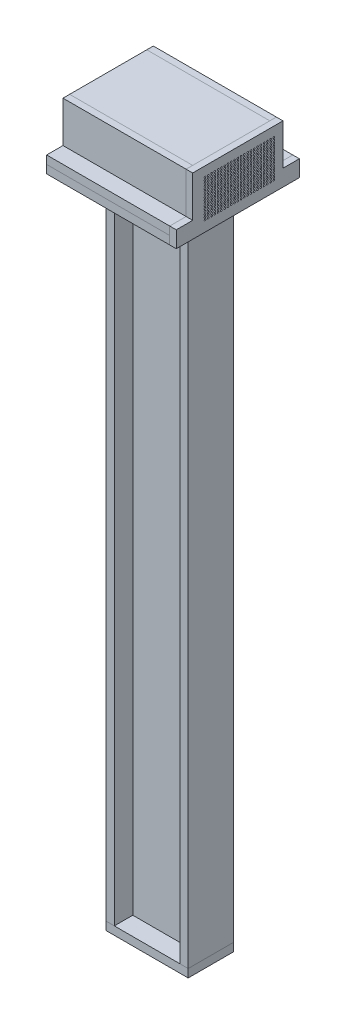
SolidWorks part; units mm, degrees
ref_plane "Front Plane" through (0, 0, 0) normal (0, 0, 1) x (1, 0, 0)
ref_plane "Top Plane" through (0, 0, 0) normal (0, 1, 0) x (1, 0, 0)
ref_plane "Right Plane" through (0, 0, 0) normal (1, 0, 0) x (0, 0, -1)
sketch "Sketch1" plane through (0, 0, 0) normal (0, 1, 0) x (1, 0, 0)
  line L0 (0, 0) -> (0, 55)
  line L1 (0, 55) -> (100, 55)
  line L2 (100, 55) -> (100, 0)
  line L3 (100, 0) -> (0, 0)
  dimension "D1" = 55
  dimension "D2" = 100
extrude "Boss-Extrude1" add sketch "Sketch1" along normal blind 10
sketch "Sketch2" plane through (0, 10, 0) normal (0, 1, 0) x (1, 0, 0)
  line L0 (10, 55) -> (10, 32.5)
  line L1 (100, 55) -> (0, 55) construction
  line L2 (0, 0) -> (100, 0) construction
  line L3 (90, 55) -> (90, 32.5)
  line L4 (0, 55) -> (0, 0) construction
  line L5 (100, 0) -> (100, 55) construction
  line L6 (10, 27.5) -> (90, 27.5) construction
  line L7 (10, 22.5) -> (90, 22.5)
  line L8 (10, 32.5) -> (90, 32.5)
  line L9 (10, 22.5) -> (10, 0)
  line L10 (90, 22.5) -> (90, 0)
  line L11 (10, 55) -> (0, 55)
  line L12 (0, 55) -> (0, 0)
  line L13 (0, 0) -> (10, 0)
  line L14 (90, 55) -> (100, 55)
  line L15 (100, 55) -> (100, 0)
  line L16 (100, 0) -> (90, 0)
  dimension "D1" = 10
  dimension "D2" = 10
  dimension "D3" = 5
  dimension "D4" = 5
extrude "Boss-Extrude2" add sketch "Sketch2" along normal blind 800 separate body
sketch "Sketch3" plane through (0, 810, 0) normal (0, 1, 0) x (1, 0, 0)
  line L0 (-25, 102.5) -> (-25, -47.5)
  line L1 (-25, -47.5) -> (125, -47.5)
  line L2 (125, -47.5) -> (125, 102.5)
  line L3 (125, 102.5) -> (-25, 102.5)
  line L4 (100, 55) -> (0, 55) construction
  line L5 (0, 55) -> (0, 0) construction
  point P3 (50, 102.5)
  point P7 (50, 55)
  point P8 (-25, 27.5)
  point P11 (0, 27.5)
  dimension "D1" = 150
  dimension "D2" = 150
  dimension "D3" = 0
  dimension "D4" = 0
extrude "Boss-Extrude3" add sketch "Sketch3" along normal blind 10 separate body
sketch "Sketch4" plane through (0, 820, 0) normal (0, 1, 0) x (1, 0, 0)
  line L0 (-25, 82.5) -> (125, 82.5)
  line L1 (-25, 102.5) -> (-25, -47.5) construction
  line L2 (125, -47.5) -> (125, 102.5) construction
  line L3 (-25, -27.5) -> (125, -27.5)
  line L4 (125, 102.5) -> (-25, 102.5) construction
  line L5 (-25, -47.5) -> (125, -47.5) construction
  line L6 (-25, 82.5) -> (-25, 102.5)
  line L7 (-25, 102.5) -> (125, 102.5)
  line L8 (125, 102.5) -> (125, 82.5)
  line L9 (-25, -27.5) -> (-25, -47.5)
  line L10 (-25, -47.5) -> (125, -47.5)
  line L11 (125, -47.5) -> (125, -27.5)
  dimension "D1" = 20
  dimension "D2" = 20
extrude "Boss-Extrude4" add sketch "Sketch4" along normal blind 10 separate body
sketch "Sketch5" plane through (0, 820, 0) normal (0, 1, 0) x (1, 0, 0)
  line L0 (-25, 74.5) -> (125, 74.5)
  line L1 (-25, 102.5) -> (-25, -47.5) construction
  line L2 (125, -47.5) -> (125, 102.5) construction
  line L3 (-25, -19.5) -> (125, -19.5)
  line L4 (125, -27.5) -> (-25, -27.5) construction
  line L5 (-25, 82.5) -> (125, 82.5) construction
  line L6 (-25, 74.5) -> (-25, 82.5)
  line L7 (-25, 82.5) -> (125, 82.5)
  line L8 (125, 82.5) -> (125, 74.5)
  line L9 (-25, -19.5) -> (-25, -27.6203)
  line L10 (-25, -27.6203) -> (125, -27.5)
  line L11 (125, -47.5) -> (125, -27.5) construction
  line L12 (125, -27.5) -> (125, -19.5)
  dimension "D1" = 8
  dimension "D2" = 8
extrude "Boss-Extrude5" add sketch "Sketch5" along normal blind 60 separate body
sketch "Sketch6" plane through (0, 0, -74.5) normal (0, 0, 1) x (1, 0, 0)
  line L0 (-25, 872) -> (125, 872)
  line L1 (-25, 880) -> (-25, 820) construction
  line L2 (125, 880) -> (125, 820) construction
  line L3 (-25, 872) -> (-25, 880)
  line L4 (-25, 880) -> (125, 880)
  line L5 (125, 880) -> (125, 872)
  dimension "D1" = 8
extrude "Boss-Extrude6" add sketch "Sketch6" along normal up to next separate body
sketch "Sketch7" plane through (125, 0, 0) normal (1, 0, 0) x (0, 0, -1)
  line L0 (-47.5, 810) -> (-47.5, 830)
  line L1 (-47.5, 820) -> (-47.5, 810) construction
  line L2 (-47.5, 830) -> (-27.5, 830)
  line L3 (-27.5, 830) -> (-27.5, 880)
  line L4 (-27.5, 880) -> (82.5, 880)
  line L5 (82.5, 880) -> (82.5, 830)
  line L6 (82.5, 830) -> (102.5, 830)
  line L7 (102.5, 830) -> (102.5, 810)
  line L8 (102.5, 810) -> (-47.5, 810)
extrude "Boss-Extrude7" add sketch "Sketch7" along normal blind 8 separate body
sketch "Sketch8" plane through (133, 0, 0) normal (1, 0, 0) x (0, 0, -1)
  line L0 (-27.5, 880) -> (-27.5, 820) construction
  line L1 (82.5, 880) -> (-27.5, 880) construction
  circle A0 centre (-12.5, 868) radius 1
  circle A1 centre (-8.5, 868) radius 1
  circle A2 centre (-4.5, 868) radius 1
  circle A3 centre (-0.5, 868) radius 1
  circle A4 centre (3.5, 868) radius 1
  circle A5 centre (7.5, 868) radius 1
  circle A6 centre (11.5, 868) radius 1
  circle A7 centre (15.5, 868) radius 1
  circle A8 centre (19.5, 868) radius 1
  circle A9 centre (23.5, 868) radius 1
  circle A10 centre (27.5, 868) radius 1
  circle A11 centre (31.5, 868) radius 1
  circle A12 centre (35.5, 868) radius 1
  circle A13 centre (39.5, 868) radius 1
  circle A14 centre (43.5, 868) radius 1
  circle A15 centre (47.5, 868) radius 1
  circle A16 centre (51.5, 868) radius 1
  circle A17 centre (55.5, 868) radius 1
  circle A18 centre (59.5, 868) radius 1
  circle A19 centre (63.5, 868) radius 1
  circle A20 centre (67.5, 868) radius 1
  circle A21 centre (71.5, 868) radius 1
  circle A22 centre (-8.5, 865) radius 1
  circle A23 centre (-4.5, 865) radius 1
  circle A24 centre (-0.5, 865) radius 1
  circle A25 centre (3.5, 865) radius 1
  circle A26 centre (7.5, 865) radius 1
  circle A27 centre (11.5, 865) radius 1
  circle A28 centre (15.5, 865) radius 1
  circle A29 centre (19.5, 865) radius 1
  circle A30 centre (23.5, 865) radius 1
  circle A31 centre (27.5, 865) radius 1
  circle A32 centre (31.5, 865) radius 1
  circle A33 centre (35.5, 865) radius 1
  circle A34 centre (39.5, 865) radius 1
  circle A35 centre (43.5, 865) radius 1
  circle A36 centre (47.5, 865) radius 1
  circle A37 centre (51.5, 865) radius 1
  circle A38 centre (55.5, 865) radius 1
  circle A39 centre (59.5, 865) radius 1
  circle A40 centre (63.5, 865) radius 1
  circle A41 centre (67.5, 865) radius 1
  circle A42 centre (71.5, 865) radius 1
  circle A43 centre (-8.5, 862) radius 1
  circle A44 centre (-4.5, 862) radius 1
  circle A45 centre (-0.5, 862) radius 1
  circle A46 centre (3.5, 862) radius 1
  circle A47 centre (7.5, 862) radius 1
  circle A48 centre (11.5, 862) radius 1
  circle A49 centre (15.5, 862) radius 1
  circle A50 centre (19.5, 862) radius 1
  circle A51 centre (23.5, 862) radius 1
  circle A52 centre (27.5, 862) radius 1
  circle A53 centre (31.5, 862) radius 1
  circle A54 centre (35.5, 862) radius 1
  circle A55 centre (39.5, 862) radius 1
  circle A56 centre (43.5, 862) radius 1
  circle A57 centre (47.5, 862) radius 1
  circle A58 centre (51.5, 862) radius 1
  circle A59 centre (55.5, 862) radius 1
  circle A60 centre (59.5, 862) radius 1
  circle A61 centre (63.5, 862) radius 1
  circle A62 centre (67.5, 862) radius 1
  circle A63 centre (71.5, 862) radius 1
  circle A64 centre (-8.5, 859) radius 1
  circle A65 centre (-4.5, 859) radius 1
  circle A66 centre (-0.5, 859) radius 1
  circle A67 centre (3.5, 859) radius 1
  circle A68 centre (7.5, 859) radius 1
  circle A69 centre (11.5, 859) radius 1
  circle A70 centre (15.5, 859) radius 1
  circle A71 centre (19.5, 859) radius 1
  circle A72 centre (23.5, 859) radius 1
  circle A73 centre (27.5, 859) radius 1
  circle A74 centre (31.5, 859) radius 1
  circle A75 centre (35.5, 859) radius 1
  circle A76 centre (39.5, 859) radius 1
  circle A77 centre (43.5, 859) radius 1
  circle A78 centre (47.5, 859) radius 1
  circle A79 centre (51.5, 859) radius 1
  circle A80 centre (55.5, 859) radius 1
  circle A81 centre (59.5, 859) radius 1
  circle A82 centre (63.5, 859) radius 1
  circle A83 centre (67.5, 859) radius 1
  circle A84 centre (71.5, 859) radius 1
  circle A85 centre (-8.5, 856) radius 1
  circle A86 centre (-4.5, 856) radius 1
  circle A87 centre (-0.5, 856) radius 1
  circle A88 centre (3.5, 856) radius 1
  circle A89 centre (7.5, 856) radius 1
  circle A90 centre (11.5, 856) radius 1
  circle A91 centre (15.5, 856) radius 1
  circle A92 centre (19.5, 856) radius 1
  circle A93 centre (23.5, 856) radius 1
  circle A94 centre (27.5, 856) radius 1
  circle A95 centre (31.5, 856) radius 1
  circle A96 centre (35.5, 856) radius 1
  circle A97 centre (39.5, 856) radius 1
  circle A98 centre (43.5, 856) radius 1
  circle A99 centre (47.5, 856) radius 1
  circle A100 centre (51.5, 856) radius 1
  circle A101 centre (55.5, 856) radius 1
  circle A102 centre (59.5, 856) radius 1
  circle A103 centre (63.5, 856) radius 1
  circle A104 centre (67.5, 856) radius 1
  circle A105 centre (71.5, 856) radius 1
  circle A106 centre (-8.5, 853) radius 1
  circle A107 centre (-4.5, 853) radius 1
  circle A108 centre (-0.5, 853) radius 1
  circle A109 centre (3.5, 853) radius 1
  circle A110 centre (7.5, 853) radius 1
  circle A111 centre (11.5, 853) radius 1
  circle A112 centre (15.5, 853) radius 1
  circle A113 centre (19.5, 853) radius 1
  circle A114 centre (23.5, 853) radius 1
  circle A115 centre (27.5, 853) radius 1
  circle A116 centre (31.5, 853) radius 1
  circle A117 centre (35.5, 853) radius 1
  circle A118 centre (39.5, 853) radius 1
  circle A119 centre (43.5, 853) radius 1
  circle A120 centre (47.5, 853) radius 1
  circle A121 centre (51.5, 853) radius 1
  circle A122 centre (55.5, 853) radius 1
  circle A123 centre (59.5, 853) radius 1
  circle A124 centre (63.5, 853) radius 1
  circle A125 centre (67.5, 853) radius 1
  circle A126 centre (71.5, 853) radius 1
  circle A127 centre (-8.5, 850) radius 1
  circle A128 centre (-4.5, 850) radius 1
  circle A129 centre (-0.5, 850) radius 1
  circle A130 centre (3.5, 850) radius 1
  circle A131 centre (7.5, 850) radius 1
  circle A132 centre (11.5, 850) radius 1
  circle A133 centre (15.5, 850) radius 1
  circle A134 centre (19.5, 850) radius 1
  circle A135 centre (23.5, 850) radius 1
  circle A136 centre (27.5, 850) radius 1
  circle A137 centre (31.5, 850) radius 1
  circle A138 centre (35.5, 850) radius 1
  circle A139 centre (39.5, 850) radius 1
  circle A140 centre (43.5, 850) radius 1
  circle A141 centre (47.5, 850) radius 1
  circle A142 centre (51.5, 850) radius 1
  circle A143 centre (55.5, 850) radius 1
  circle A144 centre (59.5, 850) radius 1
  circle A145 centre (63.5, 850) radius 1
  circle A146 centre (67.5, 850) radius 1
  circle A147 centre (71.5, 850) radius 1
  circle A148 centre (-8.5, 847) radius 1
  circle A149 centre (-4.5, 847) radius 1
  circle A150 centre (-0.5, 847) radius 1
  circle A151 centre (3.5, 847) radius 1
  circle A152 centre (7.5, 847) radius 1
  circle A153 centre (11.5, 847) radius 1
  circle A154 centre (15.5, 847) radius 1
  circle A155 centre (19.5, 847) radius 1
  circle A156 centre (23.5, 847) radius 1
  circle A157 centre (27.5, 847) radius 1
  circle A158 centre (31.5, 847) radius 1
  circle A159 centre (35.5, 847) radius 1
  circle A160 centre (39.5, 847) radius 1
  circle A161 centre (43.5, 847) radius 1
  circle A162 centre (47.5, 847) radius 1
  circle A163 centre (51.5, 847) radius 1
  circle A164 centre (55.5, 847) radius 1
  circle A165 centre (59.5, 847) radius 1
  circle A166 centre (63.5, 847) radius 1
  circle A167 centre (67.5, 847) radius 1
  circle A168 centre (71.5, 847) radius 1
  circle A169 centre (-8.5, 844) radius 1
  circle A170 centre (-4.5, 844) radius 1
  circle A171 centre (-0.5, 844) radius 1
  circle A172 centre (3.5, 844) radius 1
  circle A173 centre (7.5, 844) radius 1
  circle A174 centre (11.5, 844) radius 1
  circle A175 centre (15.5, 844) radius 1
  circle A176 centre (19.5, 844) radius 1
  circle A177 centre (23.5, 844) radius 1
  circle A178 centre (27.5, 844) radius 1
  circle A179 centre (31.5, 844) radius 1
  circle A180 centre (35.5, 844) radius 1
  circle A181 centre (39.5, 844) radius 1
  circle A182 centre (43.5, 844) radius 1
  circle A183 centre (47.5, 844) radius 1
  circle A184 centre (51.5, 844) radius 1
  circle A185 centre (55.5, 844) radius 1
  circle A186 centre (59.5, 844) radius 1
  circle A187 centre (63.5, 844) radius 1
  circle A188 centre (67.5, 844) radius 1
  circle A189 centre (71.5, 844) radius 1
  circle A190 centre (-8.5, 841) radius 1
  circle A191 centre (-4.5, 841) radius 1
  circle A192 centre (-0.5, 841) radius 1
  circle A193 centre (3.5, 841) radius 1
  circle A194 centre (7.5, 841) radius 1
  circle A195 centre (11.5, 841) radius 1
  circle A196 centre (15.5, 841) radius 1
  circle A197 centre (19.5, 841) radius 1
  circle A198 centre (23.5, 841) radius 1
  circle A199 centre (27.5, 841) radius 1
  circle A200 centre (31.5, 841) radius 1
  circle A201 centre (35.5, 841) radius 1
  circle A202 centre (39.5, 841) radius 1
  circle A203 centre (43.5, 841) radius 1
  circle A204 centre (47.5, 841) radius 1
  circle A205 centre (51.5, 841) radius 1
  circle A206 centre (55.5, 841) radius 1
  circle A207 centre (59.5, 841) radius 1
  circle A208 centre (63.5, 841) radius 1
  circle A209 centre (67.5, 841) radius 1
  circle A210 centre (71.5, 841) radius 1
  circle A211 centre (-8.5, 838) radius 1
  circle A212 centre (-4.5, 838) radius 1
  circle A213 centre (-0.5, 838) radius 1
  circle A214 centre (3.5, 838) radius 1
  circle A215 centre (7.5, 838) radius 1
  circle A216 centre (11.5, 838) radius 1
  circle A217 centre (15.5, 838) radius 1
  circle A218 centre (19.5, 838) radius 1
  circle A219 centre (23.5, 838) radius 1
  circle A220 centre (27.5, 838) radius 1
  circle A221 centre (31.5, 838) radius 1
  circle A222 centre (35.5, 838) radius 1
  circle A223 centre (39.5, 838) radius 1
  circle A224 centre (43.5, 838) radius 1
  circle A225 centre (47.5, 838) radius 1
  circle A226 centre (51.5, 838) radius 1
  circle A227 centre (55.5, 838) radius 1
  circle A228 centre (59.5, 838) radius 1
  circle A229 centre (63.5, 838) radius 1
  circle A230 centre (67.5, 838) radius 1
  circle A231 centre (71.5, 838) radius 1
  circle A232 centre (-8.5, 835) radius 1
  circle A233 centre (-4.5, 835) radius 1
  circle A234 centre (-0.5, 835) radius 1
  circle A235 centre (3.5, 835) radius 1
  circle A236 centre (7.5, 835) radius 1
  circle A237 centre (11.5, 835) radius 1
  circle A238 centre (15.5, 835) radius 1
  circle A239 centre (19.5, 835) radius 1
  circle A240 centre (23.5, 835) radius 1
  circle A241 centre (27.5, 835) radius 1
  circle A242 centre (31.5, 835) radius 1
  circle A243 centre (35.5, 835) radius 1
  circle A244 centre (39.5, 835) radius 1
  circle A245 centre (43.5, 835) radius 1
  circle A246 centre (47.5, 835) radius 1
  circle A247 centre (51.5, 835) radius 1
  circle A248 centre (55.5, 835) radius 1
  circle A249 centre (59.5, 835) radius 1
  circle A250 centre (63.5, 835) radius 1
  circle A251 centre (67.5, 835) radius 1
  circle A252 centre (71.5, 835) radius 1
  circle A253 centre (-8.5, 832) radius 1
  circle A254 centre (-4.5, 832) radius 1
  circle A255 centre (-0.5, 832) radius 1
  circle A256 centre (3.5, 832) radius 1
  circle A257 centre (7.5, 832) radius 1
  circle A258 centre (11.5, 832) radius 1
  circle A259 centre (15.5, 832) radius 1
  circle A260 centre (19.5, 832) radius 1
  circle A261 centre (23.5, 832) radius 1
  circle A262 centre (27.5, 832) radius 1
  circle A263 centre (31.5, 832) radius 1
  circle A264 centre (35.5, 832) radius 1
  circle A265 centre (39.5, 832) radius 1
  circle A266 centre (43.5, 832) radius 1
  circle A267 centre (47.5, 832) radius 1
  circle A268 centre (51.5, 832) radius 1
  circle A269 centre (55.5, 832) radius 1
  circle A270 centre (59.5, 832) radius 1
  circle A271 centre (63.5, 832) radius 1
  circle A272 centre (67.5, 832) radius 1
  circle A273 centre (71.5, 832) radius 1
  circle A274 centre (-8.5, 829) radius 1
  circle A275 centre (-4.5, 829) radius 1
  circle A276 centre (-0.5, 829) radius 1
  circle A277 centre (3.5, 829) radius 1
  circle A278 centre (7.5, 829) radius 1
  circle A279 centre (11.5, 829) radius 1
  circle A280 centre (15.5, 829) radius 1
  circle A281 centre (19.5, 829) radius 1
  circle A282 centre (23.5, 829) radius 1
  circle A283 centre (27.5, 829) radius 1
  circle A284 centre (31.5, 829) radius 1
  circle A285 centre (35.5, 829) radius 1
  circle A286 centre (39.5, 829) radius 1
  circle A287 centre (43.5, 829) radius 1
  circle A288 centre (47.5, 829) radius 1
  circle A289 centre (51.5, 829) radius 1
  circle A290 centre (55.5, 829) radius 1
  circle A291 centre (59.5, 829) radius 1
  circle A292 centre (63.5, 829) radius 1
  circle A293 centre (67.5, 829) radius 1
  circle A294 centre (71.5, 829) radius 1
  circle A295 centre (-8.5, 826) radius 1
  circle A296 centre (-4.5, 826) radius 1
  circle A297 centre (-0.5, 826) radius 1
  circle A298 centre (3.5, 826) radius 1
  circle A299 centre (7.5, 826) radius 1
  circle A300 centre (11.5, 826) radius 1
  circle A301 centre (15.5, 826) radius 1
  circle A302 centre (19.5, 826) radius 1
  circle A303 centre (23.5, 826) radius 1
  circle A304 centre (27.5, 826) radius 1
  circle A305 centre (31.5, 826) radius 1
  circle A306 centre (35.5, 826) radius 1
  circle A307 centre (39.5, 826) radius 1
  circle A308 centre (43.5, 826) radius 1
  circle A309 centre (47.5, 826) radius 1
  circle A310 centre (51.5, 826) radius 1
  circle A311 centre (55.5, 826) radius 1
  circle A312 centre (59.5, 826) radius 1
  circle A313 centre (63.5, 826) radius 1
  circle A314 centre (67.5, 826) radius 1
  circle A315 centre (71.5, 826) radius 1
  circle A316 centre (-8.5, 823) radius 1
  circle A317 centre (-4.5, 823) radius 1
  circle A318 centre (-0.5, 823) radius 1
  circle A319 centre (3.5, 823) radius 1
  circle A320 centre (7.5, 823) radius 1
  circle A321 centre (11.5, 823) radius 1
  circle A322 centre (15.5, 823) radius 1
  circle A323 centre (19.5, 823) radius 1
  circle A324 centre (23.5, 823) radius 1
  circle A325 centre (27.5, 823) radius 1
  circle A326 centre (31.5, 823) radius 1
  circle A327 centre (35.5, 823) radius 1
  circle A328 centre (39.5, 823) radius 1
  circle A329 centre (43.5, 823) radius 1
  circle A330 centre (47.5, 823) radius 1
  circle A331 centre (51.5, 823) radius 1
  circle A332 centre (55.5, 823) radius 1
  circle A333 centre (59.5, 823) radius 1
  circle A334 centre (63.5, 823) radius 1
  circle A335 centre (67.5, 823) radius 1
  circle A336 centre (71.5, 823) radius 1
  circle A337 centre (-12.5, 865) radius 1
  circle A338 centre (-12.5, 862) radius 1
  circle A339 centre (-12.5, 859) radius 1
  circle A340 centre (-12.5, 856) radius 1
  circle A341 centre (-12.5, 853) radius 1
  circle A342 centre (-12.5, 850) radius 1
  circle A343 centre (-12.5, 847) radius 1
  circle A344 centre (-12.5, 844) radius 1
  circle A345 centre (-12.5, 841) radius 1
  circle A346 centre (-12.5, 838) radius 1
  circle A347 centre (-12.5, 835) radius 1
  circle A348 centre (-12.5, 832) radius 1
  circle A349 centre (-12.5, 829) radius 1
  circle A350 centre (-12.5, 826) radius 1
  circle A351 centre (-12.5, 823) radius 1
  dimension "D1" = 2
  dimension "D2" = 15
  dimension "D3" = 12
  dimension "D4" = 22
  dimension "D5" = 16
sketch "Sketch9" plane through (0, 0, -74.5) normal (0, 0, 1) x (1, 0, 0)
  line L0 (-17, 871.7509) -> (-17, 820)
  line L1 (-25, 820) -> (125, 820) construction
  line L2 (-25, 880) -> (-25, 820) construction
  line L3 (-17, 871.7509) -> (-25, 872)
  line L4 (-25, 872) -> (-25, 820)
  line L5 (-25, 820) -> (-17, 820)
  dimension "D1" = 8
extrude "Boss-Extrude8" add sketch "Sketch9" along normal up to next (94 mm away) separate body
extrude "Cut-Extrude2" cut sketch "Sketch8" against normal blind 8
sketch "Sketch11" plane through (-25, 0, 0) normal (-1, 0, 0) x (0, 0, 1)
  line L0 (-74.5, 846) -> (19.5, 846) construction
  line L1 (-74.5, 872) -> (-74.5, 820) construction
  line L2 (19.5, 872) -> (19.5, 820) construction
  line L3 (-27.5, 872) -> (-27.5, 820) construction
  line L4 (19.5, 872) -> (-74.5, 872) construction
  line L5 (-102.5, 820) -> (47.5, 820) construction
  circle A0 centre (-27.5, 846) radius 17.5
  dimension "D1" = 35
extrude "Boss-Extrude9" add sketch "Sketch11" along normal blind 10 separate body
sketch "Sketch12" plane through (-35, 0, 0) normal (-1, 0, 0) x (0, 0, 1)
  circle A0 centre (-27.5, 846) radius 15.5
  dimension "D1" = 31
extrude "Cut-Extrude3" cut sketch "Sketch12" against normal blind 40
